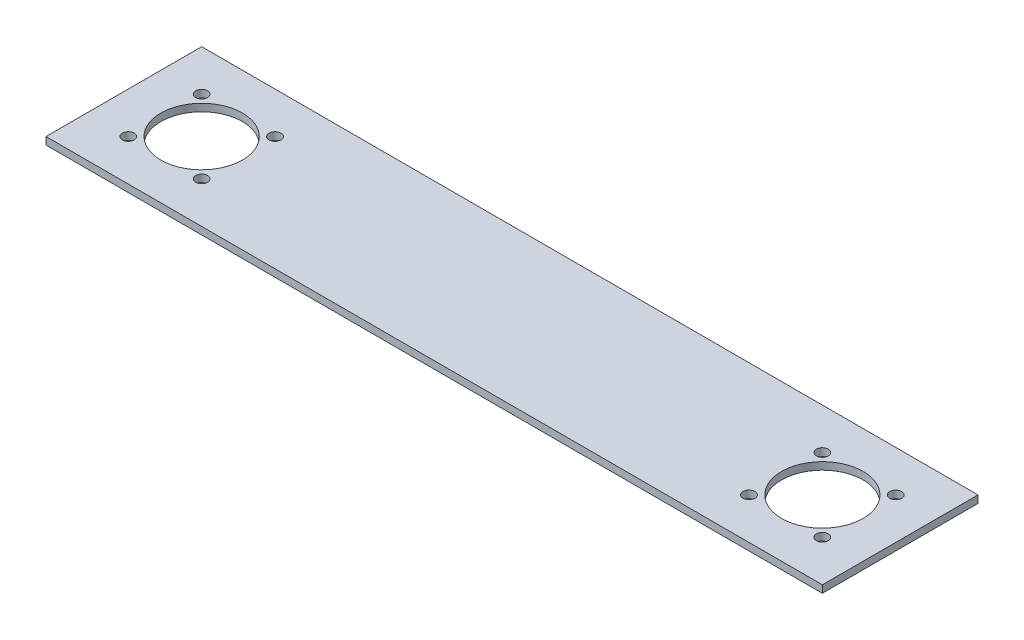
SolidWorks part; units mm, degrees
ref_plane "Front Plane" through (0, 0, 0) normal (0, 0, 1) x (1, 0, 0)
ref_plane "Top Plane" through (0, 0, 0) normal (0, 1, 0) x (1, 0, 0)
ref_plane "Right Plane" through (0, 0, 0) normal (1, 0, 0) x (0, 0, -1)
sketch "Sketch1" plane through (0, 0, 0) normal (0, 1, 0) x (1, 0, 0)
  line L0 (0, -55) -> (0, 55) construction
  line L1 (-140, -21) -> (140, -21)
  line L2 (-140, -21) -> (-140, 21)
  line L3 (-140, 21) -> (140, 21)
  line L4 (140, -21) -> (140, 21)
  line L5 (-140, -21) -> (140, 21) construction
  line L6 (-140, 21) -> (140, -21) construction
  line L7 (-104.75, 21) -> (-62.75, 21) construction
  line L8 (-104.75, 21) -> (-104.75, -21)
  line L9 (-104.75, -21) -> (-62.75, -21) construction
  line L10 (-62.75, 21) -> (-62.75, -21) construction
  line L11 (-104.75, 21) -> (-62.75, -21) construction
  line L12 (-104.75, -21) -> (-62.75, 21) construction
  line L13 (104.75, -21) -> (62.75, 21) construction
  line L14 (104.75, 21) -> (62.75, -21) construction
  line L15 (62.75, 21) -> (62.75, -21) construction
  line L16 (104.75, -21) -> (62.75, -21) construction
  line L17 (104.75, 21) -> (104.75, -21)
  line L18 (104.75, 21) -> (62.75, 21) construction
  line L19 (-21.25, 0) -> (21.25, 0) construction
  circle A0 centre (-83.75, 0) radius 62.5 construction
  circle A1 centre (-73.8505, 9.8995) radius 1.6
  circle A2 centre (-73.8505, -9.8995) radius 1.6
  circle A3 centre (-93.6495, -9.8995) radius 1.6
  circle A4 centre (-93.6495, 9.8995) radius 1.6
  circle A5 centre (83.75, 0) radius 62.5 construction
  circle A6 centre (93.6495, 9.8995) radius 1.6
  circle A7 centre (93.6495, -9.8995) radius 1.6
  circle A8 centre (73.8505, -9.8995) radius 1.6
  circle A9 centre (73.8505, 9.8995) radius 1.6
  circle A10 centre (0, 0) radius 25 construction
  circle A11 centre (-83.75, 0) radius 11
  circle A12 centre (83.75, 0) radius 11
  circle A13 centre (-83.75, 0) radius 14 construction
  point P0 (0, 0)
  point P23 (-83.75, 0)
  point P43 (83.75, 0)
  point P45 (0, 0)
  dimension "D3" = 125
  dimension "D5" = 3.2
  dimension "D8" = 167.5
  dimension "D10" = 50
  dimension "D11" = 22
  dimension "D7" = 28
  dimension "D1" = 42
  dimension "D2" = 280
  dimension "D4" = 42
  dimension "D9" = 42.5
  dimension "D6" = 4
extrude "Boss-Extrude1" add sketch "Sketch1" along normal blind 2 contours L17 L3 L8 L1 A8 A6 A4 A3 A2 A1 A7 A9 region at (0, 0, 0)
